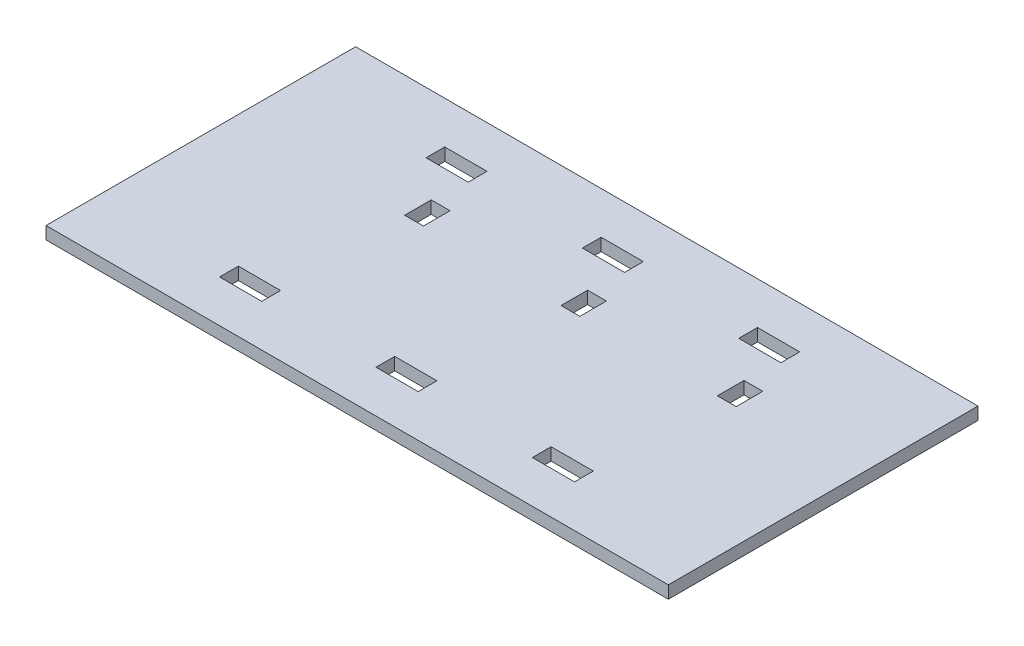
SolidWorks part; units mm, degrees
ref_plane "Front Plane" through (0, 0, 0) normal (0, 0, 1) x (1, 0, 0)
ref_plane "Top Plane" through (0, 0, 0) normal (0, 1, 0) x (1, 0, 0)
ref_plane "Right Plane" through (0, 0, 0) normal (1, 0, 0) x (0, 0, -1)
sketch "Sketch1" plane through (0, 0, 0) normal (0, 1, 0) x (1, 0, 0)
  line L1 (-50.546, -25.146) -> (50.546, -25.146)
  line L2 (-50.546, -25.146) -> (-50.546, 25.146)
  line L3 (-50.546, 25.146) -> (50.546, 25.146)
  line L4 (50.546, -25.146) -> (50.546, 25.146)
  line L5 (0, 25.146) -> (0, -25.146) construction
  line L6 (-50.546, 0) -> (50.546, 0) construction
  point P0 (0, 0)
  dimension "D1" = 50.292
  dimension "D2" = 101.092
extrude "Boss-Extrude1" add sketch "Sketch1" along normal blind 2.032
sketch "Sketch2" plane through (0, 2.032, 0) normal (0, 1, 0) x (1, 0, 0)
  line L0 (2.54, 5.425) -> (5.588, 5.425)
  line L1 (2.54, 5.425) -> (2.54, 9.743)
  line L2 (5.588, 5.425) -> (5.588, 9.743)
  line L3 (2.54, 9.743) -> (5.588, 9.743)
  circle A0 centre (4.064, 0) radius 5.635 construction
  dimension "D1" = 11.27
  dimension "D2" = 4.064
  dimension "D3" = 3.048
  dimension "D4" = 4.318
extrude "Wire Hole" cut sketch "Sketch2" against normal through all contours L3 L1 L0 L2 region at (4.064, 2.032, -7.584)
sketch "Sketch3" plane through (0, 2.032, 0) normal (0, 1, 0) x (1, 0, 0)
  line L0 (-3.81, 15.24) -> (3.048, 15.24)
  line L1 (-3.81, 15.24) -> (-3.81, 18.288)
  line L2 (3.048, 15.24) -> (3.048, 18.288)
  line L3 (-3.81, 18.288) -> (3.048, 18.288)
  line L4 (-55, 0) -> (55, 0) construction
  dimension "D1" = 3.048
  dimension "D2" = 6.858
  dimension "D3" = 3.048
  dimension "D4" = 15.24
extrude "Cut-Extrude2" cut sketch "Sketch3" against normal through all
mirror "Mirror1" about plane through (0, 0, 0) normal (0, 0, 1) of "Cut-Extrude2"
pattern_linear "LPattern1" count 2 spacing 25.4 along (-1, 0, 0) count 2 spacing 25.4 along (1, 0, 0) of "Wire Hole", "Cut-Extrude2", "Mirror1"
equation "\"Arrow Height\"= 1in"
equation "\"Button Height\"= 2in"
equation "\"Button Width\"= 4in"
equation "\"Haptic Diameter\"= 10mm"
equation "\"Haptic Thickness\"= 2.7mm"
equation "\"D1@Sketch1\"=\"Button Height\"-\"Tolerance\""
equation "\"D2@Sketch1\"=\"Button Width\"-\"Tolerance\""
equation "\"Arrow Spacing\"= 1in"
equation "\"Arrow Width\"= 0.75in"
equation "\"Haptic Wire Angle\"= 63.43"
equation "\"Haptic Wire Width\"= .1in"
equation "\"Hatic Wire Height\"= .15in"
equation "\"D1@Sketch2\"=\"Haptic Diameter\"+.05"
equation "\"D3@Sketch2\"=\"Haptic Wire Width\"+.02"
equation "\"D4@Sketch2\"=\"Hatic Wire Height\"+.02"
equation "\"Tolerance\"= .02in"
